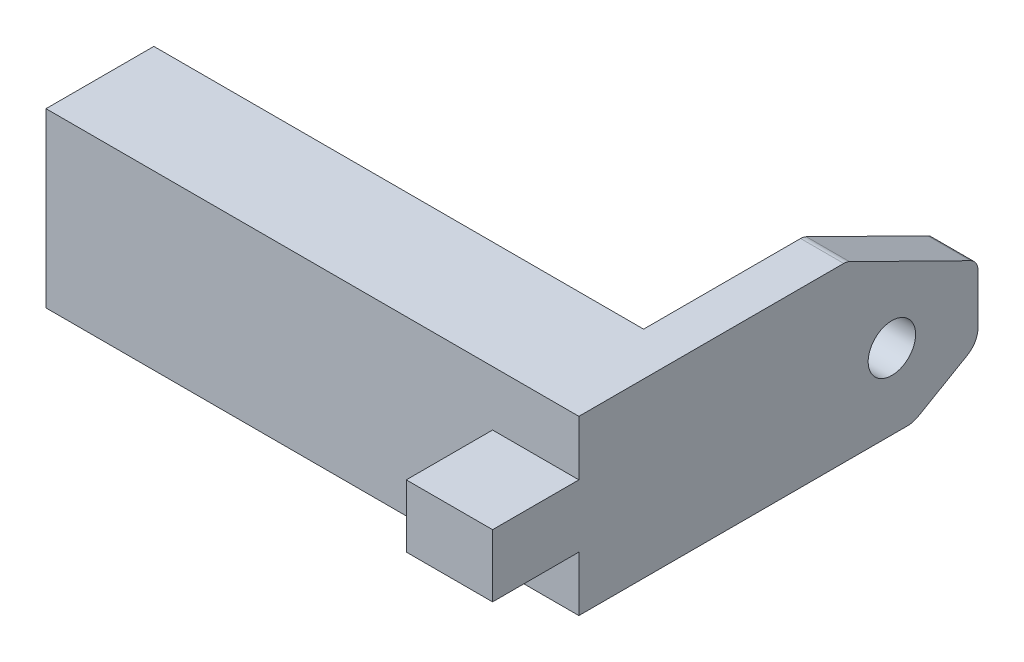
SolidWorks part; units mm, degrees
material "PLA"
ref_plane "Front Plane" through (0, 0, 0) normal (0, 0, 1) x (1, 0, 0)
ref_plane "Top Plane" through (0, 0, 0) normal (0, 1, 0) x (1, 0, 0)
ref_plane "Right Plane" through (0, 0, 0) normal (1, 0, 0) x (0, 0, -1)
sketch "Sketch1" plane through (0, 0, 0) normal (1, 0, 0) x (0, 0, -1)
  line L1 (-35.9146, 20.1296) -> (56.5854, 20.1296)
  line L2 (-35.9146, 20.1296) -> (-35.9146, -19.8704)
  line L3 (-35.9146, -19.8704) -> (56.5854, -19.8704)
  line L4 (56.5854, 20.1296) -> (56.5854, -19.8704)
  dimension "D1" = 92.5
  dimension "D2" = 40
extrude "Boss-Extrude1" add sketch "Sketch1" along normal blind 10
sketch "Sketch4" plane through (0, 0, 0) normal (-1, 0, 0) x (0, 0, 1)
  line L11 (-56.5854, 20.1296) -> (35.9146, 20.1296) construction
  line L12 (10.9146, 20.1296) -> (35.9146, 20.1296)
  line L13 (10.9146, 20.1296) -> (10.9146, -19.8704)
  line L14 (10.9146, -19.8704) -> (35.9146, -19.8704)
  line L15 (35.9146, 20.1296) -> (35.9146, -19.8704)
  line L16 (10.9146, 20.1296) -> (35.9146, -19.8704) construction
  line L17 (10.9146, -19.8704) -> (35.9146, 20.1296) construction
  line L18 (18.2896, 12.7546) -> (18.2896, -12.4954)
  line L19 (18.2896, -12.4954) -> (28.5396, -12.4954)
  line L20 (28.5396, 12.7546) -> (28.5396, -12.4954)
  line L21 (18.2896, 12.7546) -> (28.5396, 12.7546)
  point P4 (23.4146, 0.1296)
  dimension "D1" = 25
  dimension "D2" = 7.375
sketch "Sketch5" plane through (0, 0, 0) normal (-1, 0, 0) x (0, 0, 1)
  line L0 (35.9146, -19.8704) -> (-56.5854, -19.8704) construction
  line L2 (35.9146, 20.1296) -> (35.9146, -19.8704) construction
  circle A0 centre (-36.6254, -2.4304) radius 5.5
  dimension "D1" = 11
  dimension "D2" = 17.44
  dimension "D3" = 72.54
extrude "Cut-Extrude1" cut sketch "Sketch5" against normal blind 27
extrude "Boss-Extrude7" add sketch "Sketch4" along normal blind 113.5
fillet "Fillet1" radius 3 4 edges at (-113.5, -12.4954, 23.4146) (-113.5, 0.1296, 28.5396) (-113.5, 12.7546, 23.4146) (-113.5, 0.1296, 18.2896)
chamfer "Chamfer1" distance 15 angle 63.75 1 edges at (5, 20.1296, -56.5854) first distance on face at (5, 0.1296, -56.5854)
fillet "Fillet3" radius 3 2 edges at (5, 20.1296, -26.1684) (5, 5.1296, -56.5854)
chamfer "Chamfer3" distance 15 angle 30 1 edges at (5, -19.8704, -56.5854) first distance on face at (-34.5, -19.8704, -3.252)
fillet "Fillet7" radius 5 2 edges at (5, -19.8704, -41.5854) (5, -11.2102, -56.5854)
ref_plane "Plane1" through (10, 20.1296, 35.9146) normal (0, 0, 1) x (1, 0, 0)
sketch "Sketch7" plane through (10, 20.1296, 35.9146) normal (0, 0, 1) x (1, 0, 0)
  line L0 (-20, 0) -> (0, 0) construction
  line L1 (0, 0) -> (-123.5, 0) construction
  line L2 (0, 0) -> (0, -40) construction
  line L3 (-10, 0) -> (-10, -40) construction
  line L4 (0, -40) -> (-123.5, -40) construction
  line L6 (-20, -12.75) -> (0, -12.75)
  line L7 (-20, -12.75) -> (-20, -27.25)
  line L8 (-20, -27.25) -> (0, -27.25)
  line L9 (0, -12.75) -> (0, -27.25)
  line L10 (-20, -12.75) -> (0, -27.25) construction
  line L11 (-20, -27.25) -> (0, -12.75) construction
  point P10 (-10, -20)
  dimension "D1" = 20
  dimension "D2" = 14.5
extrude "Boss-Extrude8" add sketch "Sketch7" along normal blind 20
